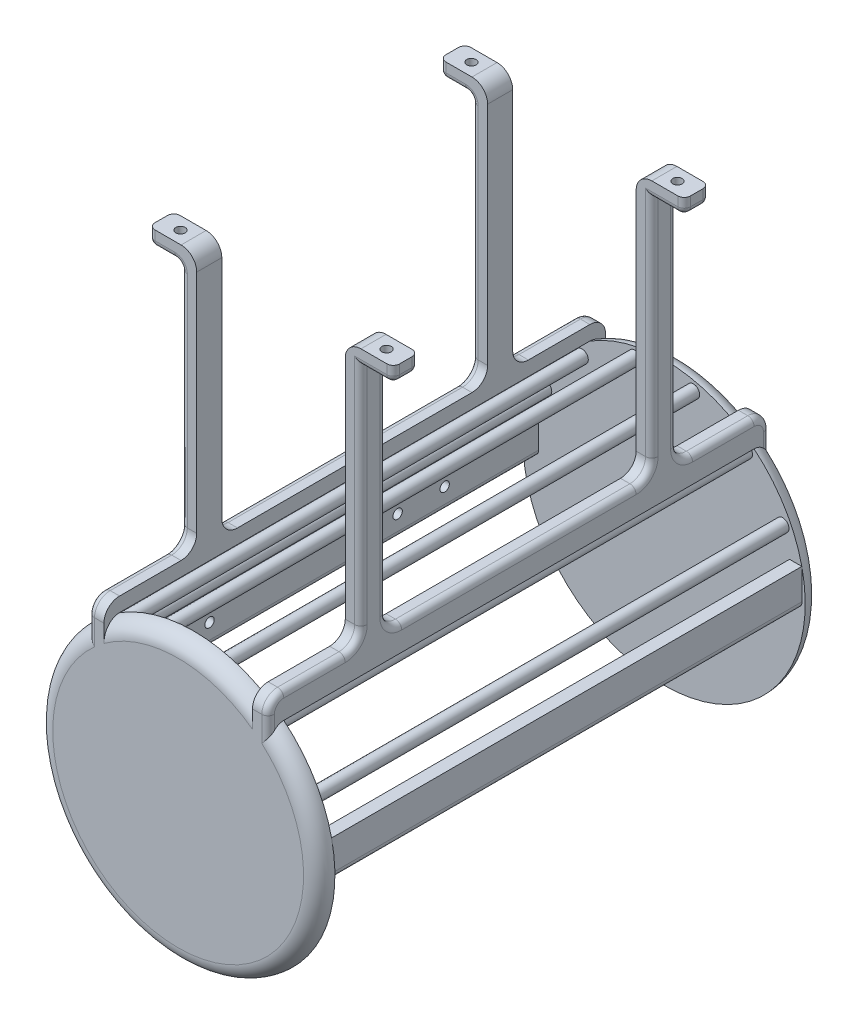
SolidWorks part; units mm, degrees
ref_plane "Front Plane" through (0, 0, 0) normal (0, 0, 1) x (1, 0, 0)
ref_plane "Top Plane" through (0, 0, 0) normal (0, 1, 0) x (1, 0, 0)
ref_plane "Right Plane" through (0, 0, 0) normal (1, 0, 0) x (0, 0, -1)
sketch "Sketch1" plane through (0, 0, 0) normal (0, 0, 1) x (1, 0, 0)
  circle A0 centre (0, 0) radius 45
  dimension "D1" = 90
extrude "Boss-Extrude1" add sketch "Sketch1" along normal blind 5
sketch "Sketch2" plane through (0, 0, 5) normal (0, 0, 1) x (1, 0, 0)
  circle A0 centre (-42, 0) radius 2
  circle A2 centre (-37.8406, 18.2236) radius 2
  circle A3 centre (-26.1862, 32.8377) radius 2
  circle A4 centre (-9.3451, 40.9479) radius 2
  circle A5 centre (9.3471, 40.9479) radius 2
  circle A6 centre (26.1882, 32.8377) radius 2
  circle A7 centre (37.8426, 18.2236) radius 2
  circle A8 centre (42.002, 0) radius 2
  point P22 (0.001, 0)
  dimension "D1" = 4
  dimension "D2" = 42
  dimension "D3" = 8
extrude "Boss-Extrude2" add sketch "Sketch2" along normal blind 150 contours A3 | A4 | A5 | A8 | A7 | A6 | A2 | A0
sketch "Sketch3" plane through (0, 0, 155) normal (0, 0, 1) x (1, 0, 0)
  circle A0 centre (0, 0) radius 45
extrude "Boss-Extrude3" add sketch "Sketch3" along normal blind 5
sketch "Sketch4" plane through (0, 0, 0) normal (0, 0, -1) x (-1, 0, 0)
  line L0 (-28.6882, 34.6697) -> (-28.6882, 42.8377)
  line L1 (-28.6882, 42.8377) -> (-23.6882, 42.8377)
  line L2 (-23.6882, 42.8377) -> (-23.6882, 38.2605)
  line L3 (0, 0) -> (0, 10.4257) construction
  line L4 (23.6882, 42.8377) -> (23.6882, 38.2605)
  line L5 (28.6882, 42.8377) -> (23.6882, 42.8377)
  line L6 (28.6882, 34.6697) -> (28.6882, 42.8377)
  arc A1 (-23.6882, 38.2605) -> (-28.6882, 34.6697) centre (0, 0) ccw
  arc A2 (23.6882, 38.2605) -> (28.6882, 34.6697) centre (0, 0) cw
extrude "Boss-Extrude4" add sketch "Sketch4" against normal up to surface (160 mm away) up to face at (45, 0, 160)
fillet "Fillet1" radius 5 4 edges at (-26.1882, 42.8377, 160) (-26.1882, 42.8377, 0) (26.1882, 42.8377, 160) (26.1882, 42.8377, 0)
fillet "Fillet2" radius 5 4 edges at (0, 45, 160) (0, -45, 160) (0, 45, 0) (0, -45, 0)
ref_plane "Plane1" through (0, 120, 0) normal (0, 1, 0) x (1, 0, 0)
sketch "Sketch5" plane through (0, 120, 0) normal (0, 1, 0) x (1, 0, 0)
  line L1 (-39, -37.61) -> (-24, -37.61)
  line L2 (-39, -37.61) -> (-39, -29.61)
  line L3 (-39, -29.61) -> (-24, -29.61)
  line L4 (-24, -37.61) -> (-24, -29.61)
  line L5 (-39, -37.61) -> (-24, -29.61) construction
  line L6 (-39, -29.61) -> (-24, -37.61) construction
  line L8 (0, 0) -> (0, -160)
  line L9 (-23.6882, -160) -> (23.6882, -160) construction
  line L10 (-23.6882, -155) -> (-23.6882, -5) construction
  line L13 (-45, -5) -> (45, -5) construction
  line L14 (-5.3022, -80) -> (13.8782, -80) construction
  line L15 (-39, -130.39) -> (-24, -122.39) construction
  line L16 (-39, -122.39) -> (-24, -130.39) construction
  line L17 (-39, -122.39) -> (-39, -130.39)
  line L18 (-39, -130.39) -> (-24, -130.39)
  line L19 (-24, -122.39) -> (-24, -130.39)
  line L20 (-39, -122.39) -> (-24, -122.39)
  line L21 (39, -122.39) -> (24, -130.39) construction
  line L22 (39, -130.39) -> (24, -122.39) construction
  line L23 (39, -29.61) -> (24, -37.61) construction
  line L24 (39, -37.61) -> (24, -29.61) construction
  line L25 (39, -122.39) -> (24, -122.39)
  line L26 (24, -122.39) -> (24, -130.39)
  line L27 (39, -130.39) -> (24, -130.39)
  line L28 (39, -122.39) -> (39, -130.39)
  line L29 (24, -37.61) -> (24, -29.61)
  line L30 (39, -29.61) -> (24, -29.61)
  line L31 (39, -37.61) -> (39, -29.61)
  line L32 (39, -37.61) -> (24, -37.61)
  circle A0 centre (-32.865, -33.61) radius 1.5
  circle A1 centre (-32.865, -126.39) radius 1.5
  circle A2 centre (32.865, -33.61) radius 1.5
  circle A3 centre (32.865, -126.39) radius 1.5
  dimension "D1" = 3
  dimension "D2" = 3
  dimension "D3" = 3
  dimension "D4" = 3
  dimension "D5" = 92.78
  dimension "D6" = 65.73
  dimension "D8" = 28.61
  dimension "D7" = 32.865
  dimension "D9" = 8
  dimension "D10" = 4
  dimension "D11" = 15
  dimension "D12" = 24
extrude "Boss-Extrude5" add sketch "Sketch5" along normal blind 5 separate body contours L28 L25 L26 L27 A3 | L20 L17 L18 L19 A1 | L32 L31 L30 L29 A2 | L1 L4 L3 L2 A0
sketch "Sketch6" plane through (0, 42.8377, 0) normal (0, 1, 0) x (1, 0, 0)
  line L0 (23.6882, -155) -> (23.6882, -5) construction
  line L1 (23.6882, -29.61) -> (28.6882, -29.61)
  line L2 (23.6882, -29.61) -> (23.6882, -37.61)
  line L3 (23.6882, -37.61) -> (28.6882, -37.61)
  line L4 (28.6882, -29.61) -> (28.6882, -37.61)
  line L5 (28.6882, -155) -> (28.6882, -5) construction
  line L6 (39, -37.61) -> (24, -37.61) construction
  line L7 (-23.6882, -155) -> (-23.6882, -5) construction
  line L8 (-23.6882, -29.61) -> (-28.6882, -29.61)
  line L9 (-23.6882, -29.61) -> (-23.6882, -37.61)
  line L10 (-23.6882, -37.61) -> (-28.6882, -37.61)
  line L11 (-28.6882, -29.61) -> (-28.6882, -37.61)
  line L12 (-39, -37.61) -> (-24, -37.61) construction
  line L13 (-28.6882, -155) -> (-28.6882, -5) construction
  line L14 (39, -122.39) -> (24, -122.39) construction
  line L15 (23.6882, -130.39) -> (28.6882, -130.39)
  line L16 (23.6882, -130.39) -> (23.6882, -122.39)
  line L17 (23.6882, -122.39) -> (28.6882, -122.39)
  line L18 (28.6882, -130.39) -> (28.6882, -122.39)
  line L19 (-39, -122.39) -> (-24, -122.39) construction
  line L20 (-23.6882, -130.39) -> (-28.6882, -130.39)
  line L21 (-23.6882, -130.39) -> (-23.6882, -122.39)
  line L22 (-23.6882, -122.39) -> (-28.6882, -122.39)
  line L23 (-28.6882, -130.39) -> (-28.6882, -122.39)
extrude "Boss-Extrude6" add sketch "Sketch6" along normal up to surface (77.1623 mm away) up to face at (-32.865, 120, 35.11)
sketch "Sketch7" plane through (0, 120, 0) normal (0, 1, 0) x (1, 0, 0)
  line L1 (-23.6882, -29.61) -> (-24, -29.61)
  line L2 (-23.6882, -29.61) -> (-23.6882, -37.61)
  line L3 (-23.6882, -37.61) -> (-24, -37.61)
  line L4 (-24, -29.61) -> (-24, -37.61)
  line L5 (24, -29.61) -> (23.6882, -29.61)
  line L6 (24, -29.61) -> (24, -37.61)
  line L7 (24, -37.61) -> (23.6882, -37.61)
  line L8 (23.6882, -29.61) -> (23.6882, -37.61)
  line L9 (-23.6882, -122.39) -> (-24, -122.39)
  line L10 (-23.6882, -122.39) -> (-23.6882, -130.39)
  line L11 (-23.6882, -130.39) -> (-24, -130.39)
  line L12 (-24, -122.39) -> (-24, -130.39)
  line L13 (23.6882, -122.39) -> (24, -122.39)
  line L14 (23.6882, -122.39) -> (23.6882, -130.39)
  line L15 (23.6882, -130.39) -> (24, -130.39)
  line L16 (24, -122.39) -> (24, -130.39)
extrude "Boss-Extrude7" add sketch "Sketch7" along normal up to surface (5 mm away) up to face at (-32.865, 125, 35.11)
fillet "Fillet3" radius 5 12 edges at (26.1882, 42.8377, 29.61) (26.1882, 42.8377, 37.61) (26.1882, 42.8377, 122.39) (26.1882, 42.8377, 130.39) (23.6882, 125, 126.39) (23.6882, 125, 33.61) (-23.6882, 125, 33.61) (-23.6882, 125, 126.39) (-26.1882, 42.8377, 122.39) (-26.1882, 42.8377, 29.61) (-26.1882, 42.8377, 37.61) (-26.1882, 42.8377, 130.39)
fillet "Fillet4" radius 2 52 edges at (-33.8441, 120, 37.61) (-28.6882, 32.8561, 0) (-28.6882, 83.9189, 37.61) (-28.6882, 32.8561, 160) (-28.6882, 41.3732, 1.4645) (-28.6882, 44.3022, 39.0745) (-28.6882, 41.3732, 158.5355) (-28.6882, 42.8377, 14.805) (-28.6882, 42.8377, 80) (-28.6882, 42.8377, 145.195) (-28.6882, 44.3022, 28.1455) (-28.6882, 44.3022, 120.9255) (-28.6882, 44.3022, 131.8545) (-28.6882, 83.9189, 29.61) (-28.6882, 83.9189, 122.39) (-28.6882, 83.9189, 130.39) (28.6882, 83.9189, 29.61) (28.6882, 44.3022, 28.1455) (28.6882, 32.8561, 0) (28.6882, 41.3732, 1.4645) (28.6882, 32.8561, 160) (28.6882, 41.3732, 158.5355) (28.6882, 42.8377, 145.195) (28.6882, 44.3022, 131.8545) (28.6882, 83.9189, 122.39) (28.6882, 44.3022, 120.9255) (28.6882, 83.9189, 37.61) (28.6882, 44.3022, 39.0745) (28.6882, 42.8377, 14.805) (28.6882, 83.9189, 130.39) (33.8441, 120, 130.39) (33.8441, 120, 122.39) (39, 120, 126.39) (39, 122.5, 130.39) (39, 122.5, 122.39) (-39, 122.5, 130.39) (-39, 122.5, 122.39) (-39, 122.5, 37.61) (-39, 122.5, 29.61) (39, 122.5, 37.61) (39, 122.5, 29.61) (33.8441, 120, 37.61) (33.8441, 120, 29.61) (39, 120, 33.61) (28.6882, 42.8377, 80) (-33.8441, 120, 29.61) (-39, 120, 33.61) (-28.6882, 120, 33.61) (-28.6882, 120, 126.39) (-33.8441, 120, 122.39) (-39, 120, 126.39) (-33.8441, 120, 130.39)
sketch "Sketch8" plane through (0, 0, 5) normal (0, 0, 1) x (1, 0, 0)
  line L0 (-44, 0) -> (-43.9167, 9.8142)
  line L1 (-43.9167, 9.8142) -> (-42, 9.8142)
  line L2 (-40, 0) -> (-40, 9.8142)
  line L3 (-40, 9.8142) -> (-42, 9.8142)
  line L4 (0, 0) -> (0, 8.2908) construction
  line L5 (40, 9.8142) -> (42, 9.8142)
  line L6 (40, 0) -> (40, 9.8142)
  line L7 (43.9167, 9.8142) -> (42, 9.8142)
  line L8 (44, 0) -> (43.9167, 9.8142)
  circle A0 centre (-42, 0) radius 2 construction
  arc A1 (-28.6882, 34.6697) -> (28.6882, 34.6697) centre (0, 0) ccw construction
  arc A2 (-40, 0) -> (-44, 0) centre (-42, 0) ccw
  arc A3 (40, 0) -> (44, 0) centre (42, 0) cw
  circle M1 centre (-42, 0) radius 2
  circle M5 centre (42.002, 0) radius 2
extrude "Boss-Extrude8" add sketch "Sketch8" along normal up to surface (150 mm away) contours L2 L3 L1 L0 M1 | L6 A3 L8 L7 L5 M5 up to face at (-24.1862, 32.8377, 155)
sketch "Sketch9" plane through (-43.9968, 0.3732, 0) normal (-1, 0.0085, 0) x (0, 0, 1)
  line L0 (5, -0.3393) -> (5, 9.4414) construction
  line L1 (155, 34.9118) -> (155, 10.1864) construction
  line L2 (5, 4.551) -> (155, 4.551) construction
  line L3 (155, -0.3393) -> (155, 9.4414) construction
  circle A0 centre (35, 4.551) radius 1.5
  circle A1 centre (50, 4.551) radius 1.5
  circle A2 centre (110, 4.551) radius 1.5
  circle A3 centre (125, 4.551) radius 1.5
  dimension "D1" = 15
  dimension "D2" = 15
  dimension "D3" = 30
  dimension "D4" = 30
  dimension "D5" = 3
  dimension "D6" = 3
  dimension "D7" = 3
  dimension "D8" = 3
extrude "Cut-Extrude1" cut sketch "Sketch9" against normal up to surface (3.9711 mm away)
